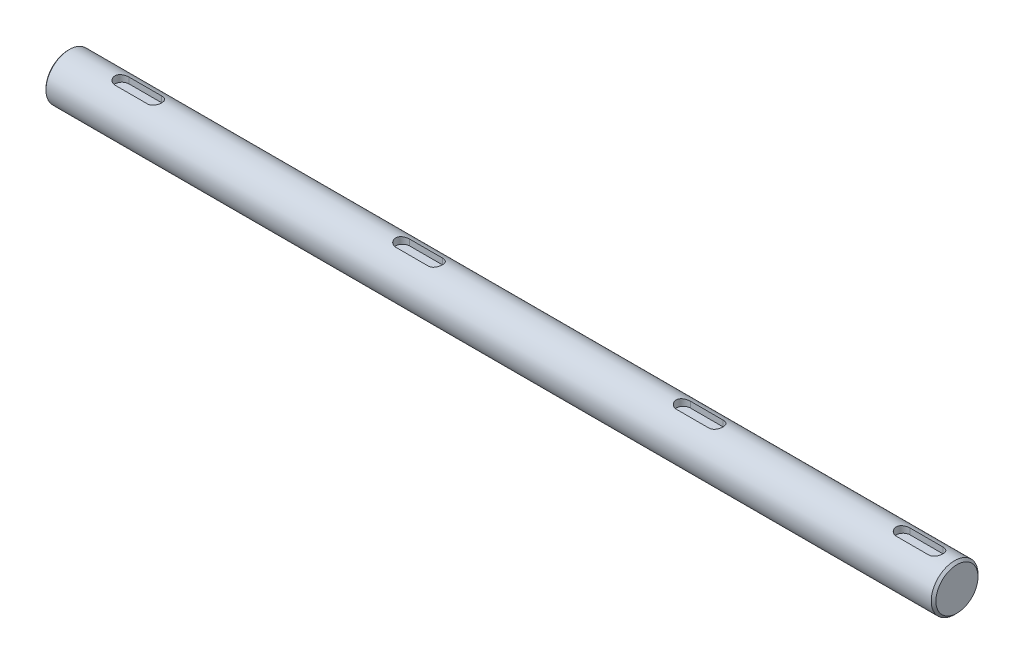
SolidWorks part; units mm, degrees
other "细节项目1"
material "45"
ref_plane "前视基准面" through (0, 0, 0) normal (0, 0, 1) x (1, 0, 0)
ref_plane "上视基准面" through (0, 0, 0) normal (0, 1, 0) x (1, 0, 0)
ref_plane "右视基准面" through (0, 0, 0) normal (1, 0, 0) x (0, 0, -1)
ref_axis "基准轴1" through (88.99, 0, 0) along (-1, 0, 0)
sketch "草图1" plane through (0, 0, 0) normal (1, 0, 0) x (0, 0, -1)
  circle A0 centre (0, 0) radius 10
extrude "凸台-拉伸1" add sketch "草图1" along normal blind 300
ref_plane "基准面1" through (0, 10, 0) normal (0, 1, 0) x (1, 0, 0)
sketch "草图2" plane through (0, 10, 0) normal (0, 1, 0) x (1, 0, 0)
  line L0 (263, 3) -> (277, 3)
  line L1 (263, -3) -> (277, -3)
  arc A0 (263, 3) -> (263, -3) centre (263, 0) ccw
  arc A1 (277, 3) -> (277, -3) centre (277, 0) cw
  dimension "D1" = 3
  dimension "D2" = 14
extrude "切除-拉伸1" cut sketch "草图2" against normal blind 3
chamfer "倒角1" distance 0.5 angle 45 1 edges at (0, 0, -10)
chamfer "倒角2" distance 0.5 angle 45 1 edges at (300, 0, -10)
ref_plane "基准面2" through (150, 0, 0) normal (1, 0, 0) x (0, 0, -1)
pattern_linear "阵列(线性)1" count 3 spacing 120 along (-1, 0, 0) of "切除-拉伸1"
sketch "草图3" plane through (300, 0, 0) normal (1, 0, 0) x (0, 0, -1)
  circle A0 centre (0, 0) radius 10
extrude "凸台-拉伸2" add sketch "草图3" along normal blind 110 from offset 10 offset against normal yes
chamfer "倒角3" distance 1 angle 45 1 edges at (400, 0, -10)
ref_plane "基准面3" through (0, 7, 0) normal (0, 1, 0) x (1, 0, 0)
sketch "草图4" plane through (0, 7, 0) normal (0, 1, 0) x (1, 0, 0)
  line L0 (357, 3) -> (371, 3)
  line L1 (371, -3) -> (357, -3)
  arc A0 (357, 3) -> (357, -3) centre (357, 0) ccw
  arc A1 (371, -3) -> (371, 3) centre (371, 0) ccw
  arc A2 (277, -3) -> (277, 3) centre (277, 0) ccw construction
  dimension "D1" = 6
  dimension "D3" = 80
  dimension "D2" = 14
extrude "切除-拉伸2" cut sketch "草图4" along normal blind 60
sketch "草图5" plane through (400, 0, 0) normal (1, 0, 0) x (0, 0, -1)
  circle A0 centre (0, 0) radius 10
extrude "切除-拉伸3" cut sketch "草图5" against normal blind 20
chamfer "倒角4" distance 1 angle 45 1 edges at (380, 0, -10)
